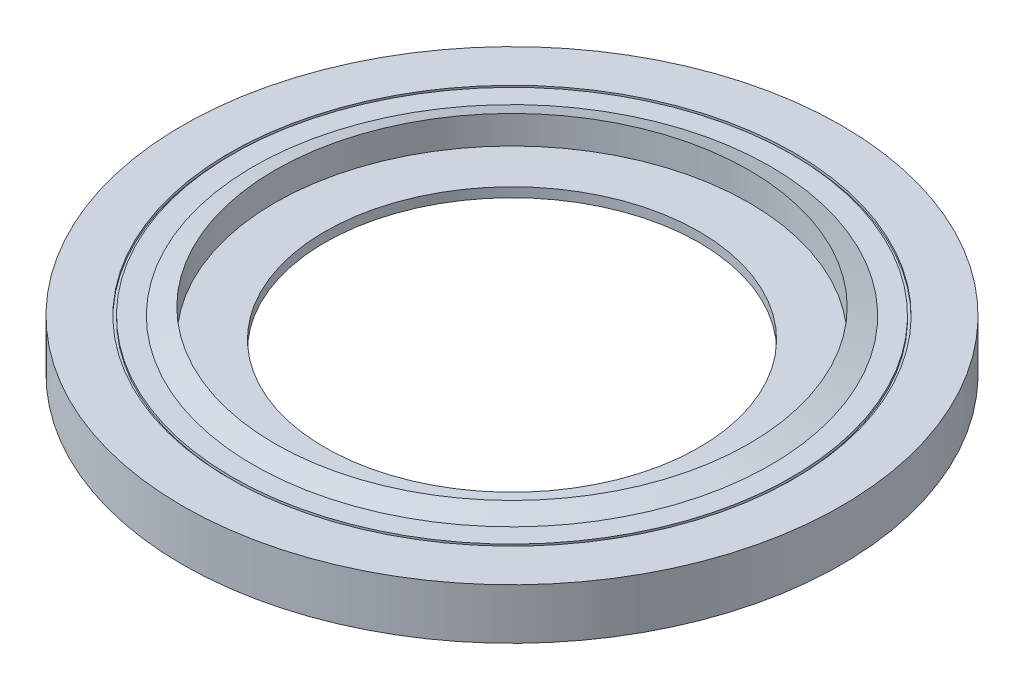
SolidWorks part; units mm, degrees
ref_plane "Front Plane" through (0, 0, 0) normal (0, 0, 1) x (1, 0, 0)
ref_plane "Top Plane" through (0, 0, 0) normal (0, 1, 0) x (1, 0, 0)
ref_plane "Right Plane" through (0, 0, 0) normal (1, 0, 0) x (0, 0, -1)
sketch "Sketch1" plane through (0, 0, 0) normal (0, 0, 1) x (1, 0, 0)
  line L0 (0, 0) -> (0, 5.1453) construction
  line L1 (7.38, -0.1875) -> (7.38, 0.1875)
  line L2 (7.38, -0.1875) -> (10.2, -1) construction
  line L3 (10.2, -1) -> (11.0333, -1)
  line L4 (11.1333, -1) -> (13, -1)
  line L5 (13, -1) -> (13, 1)
  line L6 (13, 1) -> (11.1333, 1)
  line L7 (16.6173, 0) -> (-12.4517, 0) construction
  line L8 (10.2, 1) -> (11.0333, 1)
  line L9 (7.38, 0.1875) -> (10.2, 1) construction
  line L10 (11.1333, 1) -> (11.1333, 0.9)
  line L11 (11.1333, 0.9) -> (11.0333, 0.9)
  line L12 (11.0333, 0.9) -> (11.0333, 1)
  line L13 (11.0333, -0.9) -> (11.0333, -1)
  line L14 (11.1333, -0.9) -> (11.0333, -0.9)
  line L15 (11.1333, -1) -> (11.1333, -0.9)
  line L16 (10.2, 1) -> (9.35, 1.3)
  line L17 (9.35, 1.3) -> (9.35, 0.1875)
  line L18 (7.38, 0.1875) -> (9.35, 0.1875)
  line L19 (7.38, -0.1875) -> (9.35, -0.1875)
  line L20 (9.35, -1.3) -> (9.35, -0.1875)
  line L21 (10.2, -1) -> (9.35, -1.3)
  point P15 (7.38, 0)
  dimension "D2" = 0.1
  dimension "D3" = 0.1
  dimension "P" = 0.3
revolve "Revolve1" add sketch "Sketch1" angle 360 about L0
ref_axis "Axis1" through (0, 1.43, 0) along (0, -1, 0)
sketch "Sketch2" plane through (0, 0, 0) normal (0, 0, 1) x (1, 0, 0)
  line L0 (0, 0) -> (0, -4.6258) construction
  line L1 (11.1333, 1) -> (13, 1)
  line L2 (11.1333, 1) -> (11.1333, -1)
  line L3 (11.1333, -1) -> (13, -1)
  line L4 (13, 1) -> (13, -1)
  line L5 (0, 1.43) -> (0, -1.43) construction
revolve "Revolve2" [suppressed] add sketch "Sketch2" angle 360 about L0
equation "\"D4@Sketch1\"=\"d1@Sketch1\" + ( \"OD@Sketch1\" - \"d1@Sketch1\" ) / 3"
